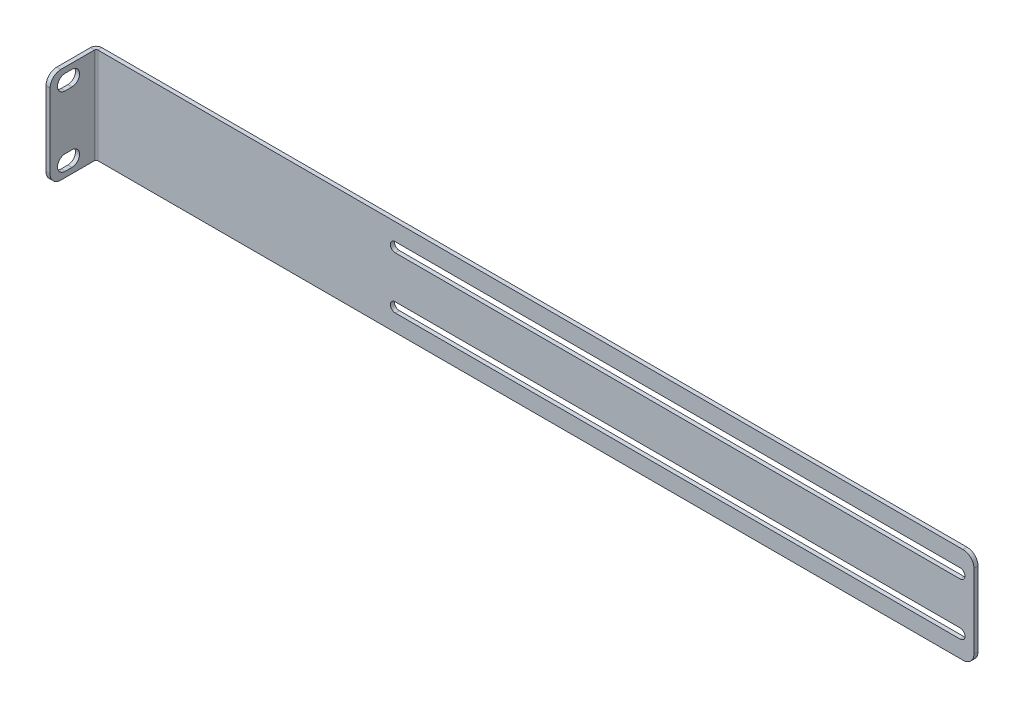
SolidWorks part; units mm, degrees
note: The reader was unsure of these and kept them because the rebuilt part matched: flange length of "Edge-Flange1".
ref_plane "Front Plane" through (0, 0, 0) normal (0, 0, 1) x (1, 0, 0)
ref_plane "Top Plane" through (0, 0, 0) normal (0, 1, 0) x (1, 0, 0)
ref_plane "Right Plane" through (0, 0, 0) normal (1, 0, 0) x (0, 0, -1)
sketch "Sketch1" plane through (0, 0, 0) normal (0, 0, 1) x (1, 0, 0)
  line L0 (406.4, 34) -> (0, 34) construction
  line L1 (0, 0) -> (406.4, 0)
  line L2 (0, 0) -> (0, 44.196)
  line L3 (0, 44.196) -> (406.4, 44.196)
  line L4 (406.4, 0) -> (406.4, 44.196)
  line L5 (406.4, 10) -> (0, 10) construction
  line L6 (139.7, 34) -> (400.05, 34) construction
  line L7 (139.7, 36.2225) -> (400.05, 36.2225)
  line L8 (139.7, 31.7775) -> (400.05, 31.7775)
  line L9 (139.7, 10) -> (400.05, 10) construction
  line L10 (139.7, 12.2225) -> (400.05, 12.2225)
  line L11 (139.7, 7.7775) -> (400.05, 7.7775)
  line L12 (373.8734, 12.7051) -> (373.8734, 7.2949) construction
  line L13 (373.8734, 36.7051) -> (373.8734, 31.2949) construction
  line L14 (371.1683, 10) -> (376.5785, 10) construction
  arc A0 (139.7, 36.2225) -> (139.7, 31.7775) centre (139.7, 34) ccw
  arc A1 (400.05, 31.7775) -> (400.05, 36.2225) centre (400.05, 34) ccw
  arc A2 (139.7, 12.2225) -> (139.7, 7.7775) centre (139.7, 10) ccw
  arc A3 (400.05, 7.7775) -> (400.05, 12.2225) centre (400.05, 10) ccw
  circle A8 centre (373.8734, 10) radius 2.7051 construction
  circle A9 centre (373.8734, 34) radius 2.7051 construction
  circle A10 centre (373.8734, 10) radius 2.7051 construction
  point P11 (269.875, 34)
  point P16 (269.875, 10)
  point P31 (373.8734, 34)
  point P32 (373.8734, 10)
  point P37 (0, 0)
  point P38 (373.8734, 10)
  dimension "D1" = 406.4
  dimension "D2" = 4.445
  dimension "D3" = 6.35
  dimension "D4" = 266.7
  dimension "D5" = 44.196
base flange "Base-Flange1" sketch "Sketch1" thickness 1.88 reverse thickness direction no parameters "D1"=0.7366
edge flange "Edge-Flange1" sketch "Sketch8" flange angle 90 flange length 23.114 flange position material inside bend radius 0.7366 thickness 1.88 relief rectangular parameters "D6"=10
sketch "Sketch8" plane through (0, 0, 0) normal (-1, 0, 0) x (0, -1, 0)
  line L2 (-44.196, 0) -> (-44.196, 21.234)
  line L3 (-44.196, 21.234) -> (0, 21.234)
  line L4 (0, 21.234) -> (0, 0)
  line L7 (-44.196, 0) -> (0, 0) construction
  line L8 (-44.196, 0) -> (0, 0)
bend "EdgeBend1" bend radius 0.7366 bend angle 90 parameters "D5"=1
sketch "Sketch9" plane through (0, 0, 0) normal (-1, 0, 0) x (0, 0, 1)
  line L0 (0.7366, 38.156) -> (21.234, 38.156) construction
  line L1 (0.7366, 0) -> (0.7366, 44.196) construction
  line L2 (21.234, 0) -> (21.234, 44.196) construction
  line L3 (21.234, 6.04) -> (0.7366, 6.04) construction
  line L4 (11.145, 38.156) -> (14.305, 38.156) construction
  line L5 (11.145, 41.656) -> (14.305, 41.656)
  line L6 (11.145, 34.656) -> (14.305, 34.656)
  line L7 (11.145, 6.04) -> (14.305, 6.04) construction
  line L8 (11.145, 9.54) -> (14.305, 9.54)
  line L9 (11.145, 2.54) -> (14.305, 2.54)
  line L10 (21.234, 44.196) -> (0.7366, 44.196) construction
  line L12 (14.305, 41.656) -> (14.305, 44.196) construction
  line L13 (14.305, 2.54) -> (14.305, 0) construction
  line L14 (0.7366, 0) -> (21.234, 0) construction
  arc A0 (11.145, 41.656) -> (11.145, 34.656) centre (11.145, 38.156) ccw
  arc A1 (14.305, 34.656) -> (14.305, 41.656) centre (14.305, 38.156) ccw
  arc A2 (11.145, 9.54) -> (11.145, 2.54) centre (11.145, 6.04) ccw
  arc A3 (14.305, 2.54) -> (14.305, 9.54) centre (14.305, 6.04) ccw
  point P10 (12.725, 38.156)
  point P15 (12.725, 6.04)
  point P23 (17.805, 38.156)
  point P24 (7.645, 38.156)
  dimension "D2" = 10.16
  dimension "D1" = 7
  dimension "D3" = 3.429
  dimension "D4" = 2.54
extrude "Cut-Extrude1" cut sketch "Sketch9" against normal up to next normal cut yes
fillet "Fillet1" radius 5 4 edges at (406.4, 0, -0.94) (406.4, 44.196, -0.94) (0.94, 0, 21.234) (0.94, 44.196, 21.234)
sketch "Bend-Lines1" [suppressed] plane through (0, 0, 0) normal (0, 1, 0) x (1, 0, 0)
sketch "Bounding-Box1" [suppressed] plane through (0, 0, 0) normal (0, 1, 0) x (1, 0, 0)
sheet metal parameters "Sheet-Metal1" thickness 1.88 parameters "D1"=0.7366
flat pattern "Flat-Pattern1" [suppressed]
sketch "Bend-Lines2" plane through (0, 0, 0) normal (0, 1, 0) x (1, 0, 0)
sketch3d "Bounding-Box2" [suppressed]
  line L0 (0, 0, 0) -> (-406.4, 0, 0) construction
  line L1 (0, 80.2205, 0) -> (-406.4, 80.2205, 0) construction
  line L2 (0, 0, 0) -> (0, 80.2205, 0) construction
  line L3 (-406.4, 0, 0) -> (-406.4, 80.2205, 0) construction
sheet metal parameters "Sheet-Metal2" thickness 1.88 parameters "D1"=0.7366
flat pattern "Flat-Pattern1"
sketch "Bend-Lines2" plane through (0, 0, 0) normal (0, 0, 1) x (1, 0, 0)
  line L0 (1.4475, 44.196) -> (1.4475, 0) construction
  line L1 (1.4475, 44.196) -> (1.4475, 0) construction
sketch3d "Bounding-Box2" [suppressed]
  line L0 (-20.2191, 0, 0) -> (406.4, 0, 0) construction
  line L1 (-20.2191, 44.196, 0) -> (406.4, 44.196, 0) construction
  line L2 (-20.2191, 0, 0) -> (-20.2191, 44.196, 0) construction
  line L3 (406.4, 0, 0) -> (406.4, 44.196, 0) construction
bend of the flat pattern "Flatten-<EdgeBend1>1"
sheet metal parameters "Sheet-Metal3" thickness 1.88 parameters "D1"=0.7366
flat pattern "Flat-Pattern1"
sketch "Bend-Lines2" plane through (0, 0, 0) normal (0, 0, 1) x (1, 0, 0)
  line L0 (1.4475, 44.196) -> (1.4475, 0) construction
  line L1 (1.4475, 44.196) -> (1.4475, 0) construction
sketch3d "Bounding-Box2" [suppressed]
  line L0 (-20.2191, 44.196, 0) -> (406.4, 44.196, 0) construction
  line L1 (-20.2191, 0, 0) -> (406.4, 0, 0) construction
  line L2 (-20.2191, 44.196, 0) -> (-20.2191, 0, 0) construction
  line L3 (406.4, 44.196, 0) -> (406.4, 0, 0) construction
bend of the flat pattern "Flatten-<EdgeBend1>1"
